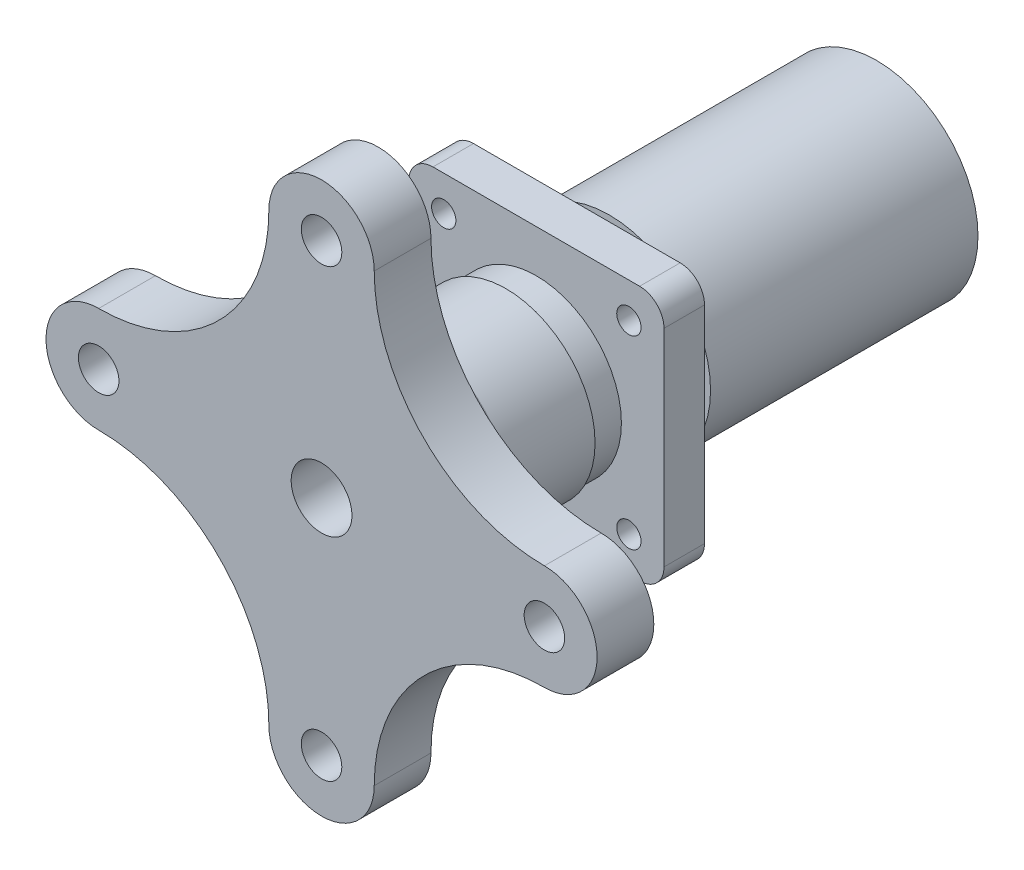
SolidWorks part; units mm, degrees
ref_plane "Front Plane" through (0, 0, 0) normal (0, 0, 1) x (1, 0, 0)
ref_plane "Top Plane" through (0, 0, 0) normal (0, 1, 0) x (1, 0, 0)
ref_plane "Right Plane" through (0, 0, 0) normal (1, 0, 0) x (0, 0, -1)
sketch "Sketch1" plane through (0, 0, 0) normal (0, 0, 1) x (1, 0, 0)
  circle A0 centre (0, 0) radius 12.75
  circle A1 centre (0, 0) radius 25
  dimension "D1" = 25.5
  dimension "D2" = 50
extrude "Boss-Extrude1" add sketch "Sketch1" along normal blind 123
ref_plane "disk_plane" through (0, 0, 74) normal (0, 0, -1) x (-1, 0, 0)
sketch "Sketch16" plane through (0, 0, 123) normal (0, 0, 1) x (1, 0, 0)
  circle A0 centre (0, 0) radius 25
  circle A1 centre (0, 0) radius 22
  dimension "D1" = 44
extrude "Cut-Extrude1" cut sketch "Sketch16" against normal blind 50
sketch "Sketch2" plane through (0, 0, 74) normal (0, 0, -1) x (-1, 0, 0)
  line L0 (0, 0) -> (46.4229, 0) construction
  line L1 (-25.5, -31.5) -> (25.5, -31.5)
  line L2 (-31.5, -25.5) -> (-31.5, 25.5)
  line L3 (-25.5, 31.5) -> (25.5, 31.5)
  line L4 (31.5, -25.5) -> (31.5, 25.5)
  line L5 (-31.5, -31.5) -> (31.5, 31.5) construction
  line L6 (-31.5, 31.5) -> (31.5, -31.5) construction
  circle A0 centre (22.8466, 22.8466) radius 3
  circle A1 centre (-22.8466, -22.8466) radius 3
  circle A2 centre (22.8466, -22.8466) radius 3
  circle A3 centre (-22.8466, 22.8466) radius 3
  arc A4 (25.5, -31.5) -> (31.5, -25.5) centre (25.5, -25.5) ccw
  arc A5 (-25.5, -31.5) -> (-31.5, -25.5) centre (-25.5, -25.5) cw
  arc A6 (-31.5, 25.5) -> (-25.5, 31.5) centre (-25.5, 25.5) cw
  arc A7 (25.5, 31.5) -> (31.5, 25.5) centre (25.5, 25.5) cw
  circle A8 centre (0, 0) radius 22
  circle A9 centre (0, 0) radius 22 construction
  point P0 (0, 0)
  dimension "D3" = 6
  dimension "D4" = 6
  dimension "D1" = 63
  dimension "D2" = 63
  dimension "D5" = 32.31
extrude "Boss-Extrude2" add sketch "Sketch2" against normal blind 10
sketch "Sketch3" plane through (0, 0, 123) normal (0, 0, 1) x (1, 0, 0)
  line L0 (0, 42) -> (0, 55) construction
  line L1 (0, 0) -> (55, 0) construction
  line L2 (0, 55) -> (21.233, 55) construction
  line L3 (55, 0) -> (55, 23.4869) construction
  line L4 (13, 55) -> (13, 33.7853) construction
  line L5 (55, 13) -> (81.8117, 13) construction
  circle A0 centre (0, 0) radius 55 construction
  circle A1 centre (0, 55) radius 5
  circle A2 centre (55, 0) radius 5
  circle A3 centre (0, -55) radius 5
  circle A4 centre (-55, 0) radius 5
  arc A5 (12.9089, 53.4636) -> (-12.9089, 53.4636) centre (0, 55) ccw
  arc A6 (53.4636, -12.9089) -> (53.4636, 12.9089) centre (55, 0) ccw
  arc A7 (-12.9089, -53.4636) -> (12.9089, -53.4636) centre (0, -55) ccw
  arc A8 (-53.4636, 12.9089) -> (-53.4636, -12.9089) centre (-55, 0) ccw
  arc A9 (13, 55) -> (55, 13) centre (55, 55) ccw
  arc A10 (55, -13) -> (13, -55) centre (55, -55) ccw
  arc A11 (-13, -55) -> (-55, -13) centre (-55, -55) ccw
  arc A12 (-55, 13) -> (-13, 55) centre (-55, 55) ccw
  circle A13 centre (0, 0) radius 7.5
  point P10 (13, 55)
  point P15 (0, 0)
  point P16 (55, 13)
  point P23 (0, 0)
  point P41 (0, 0)
  circle M2 centre (0, 0) radius 12.75
  dimension "D1" = 110
  dimension "D2" = 4
  dimension "D3" = 10
  dimension "D5" = 26
  dimension "D7" = 15
  dimension "D6" = 4
  dimension "D4" = 4
extrude "Boss-Extrude3" add sketch "Sketch3" along normal blind 14 contours A12 A8 A11 A7 A10 A6 A9 A5 A4 A3 A2 A1 | M2 | A13 M2 region at (23.9415, 23.9415, 123) region at (-12.3894, 0, 123)
sketch "Sketch4" plane through (0, 0, 74) normal (0, 0, -1) x (-1, 0, 0)
  circle A0 centre (22.8466, 22.8466) radius 9
  circle A1 centre (22.8466, -22.8466) radius 9
  circle A2 centre (-22.8466, -22.8466) radius 9
  circle A3 centre (-22.8466, 22.8466) radius 9
  point P12 (0, 0)
  dimension "D2" = 18
  dimension "D1" = 4
sketch "Sketch5" plane through (0, 0, 84) normal (0, 0, 1) x (1, 0, 0)
  circle A0 centre (22.8466, 22.8466) radius 9
  circle A1 centre (22.8466, -22.8466) radius 9
  circle A2 centre (-22.8466, -22.8466) radius 9
  circle A3 centre (-22.8466, 22.8466) radius 9
  point P12 (0, 0)
  dimension "D1" = 18
  dimension "D2" = 4
fillet "Fillet1" radius 10 1 edges at (22, 0, 123)
chamfer "Chamfer1" distance 5 angle 45 1 edges at (25, 0, 73)
ref_plane "Plane2" through (0, 0, 74) normal (0, 0, -1) x (-1, 0, 0)
sketch "Sketch6" plane through (0, 0, 74) normal (0, 0, -1) x (-1, 0, 0)
  circle A0 centre (0, 0) radius 20
  circle A1 centre (0, 0) radius 7.5
  dimension "D1" = 15
extrude "Boss-Extrude4" add sketch "Sketch6" against normal up to surface (49 mm away) and the other way blind 17.5 up to face at (32, 0, 123)
sketch "Sketch7" plane through (0, 0, 0) normal (0, 0, -1) x (-1, 0, 0)
  circle A0 centre (0, 0) radius 27.5
ref_plane "Plane4" through (0, 0, 56.75) normal (0, 0, -1) x (-1, 0, 0)
sketch "Sketch11" plane through (0, 0, 74) normal (0, 0, -1) x (-1, 0, 0)
  circle A0 centre (0, 0) radius 27.5
  circle A1 centre (0, 0) radius 21
  dimension "D1" = 42
extrude "nut_groove" cut sketch "Sketch11" along normal blind 8
sketch "Sketch13" plane through (0, 0, 56.5) normal (0, 0, -1) x (-1, 0, 0)
  circle A0 centre (0, 0) radius 12
  circle A1 centre (0, 0) radius 22.5
ref_plane "plane" through (0, 0, 84) normal (0, 0, 1) x (1, 0, 0)
sketch "Sketch15" plane through (0, 0, 84) normal (0, 0, 1) x (1, 0, 0)
  circle A0 centre (0, 0) radius 21
  circle A1 centre (0, 0) radius 27.5
  dimension "D1" = 42
extrude "bolt_groove" cut sketch "Sketch15" along normal blind 7.5
